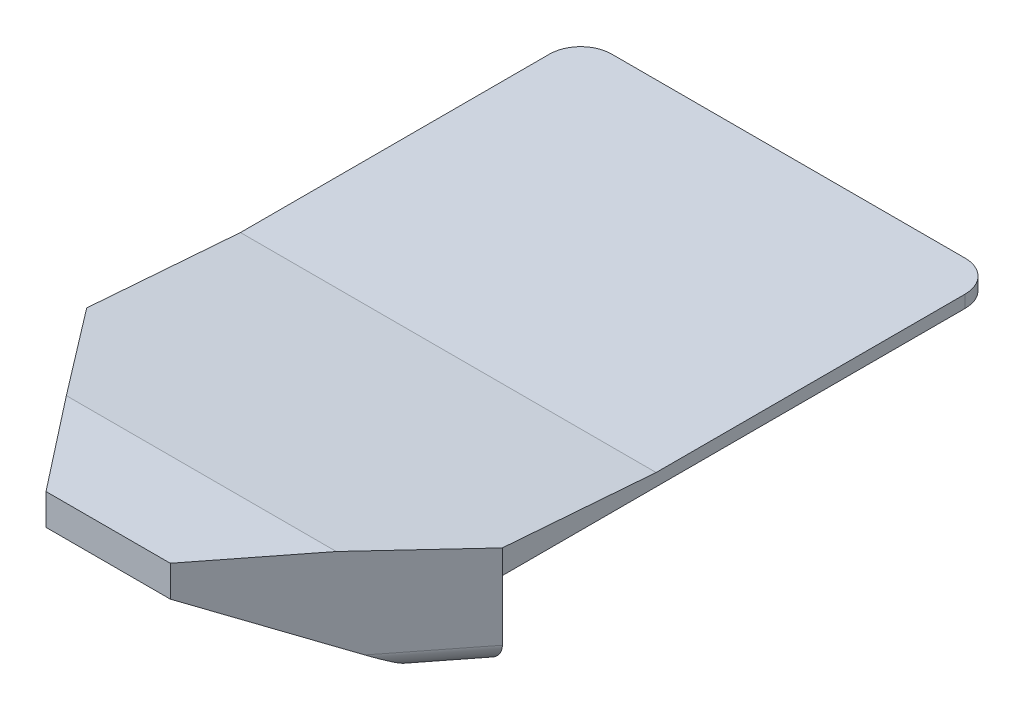
SolidWorks part; units mm, degrees
ref_plane "Front Plane" through (0, 0, 0) normal (0, 0, 1) x (1, 0, 0)
ref_plane "Top Plane" through (0, 0, 0) normal (0, 1, 0) x (1, 0, 0)
ref_plane "Right Plane" through (0, 0, 0) normal (1, 0, 0) x (0, 0, -1)
sketch "Sketch1" plane through (0, 0, 0) normal (0, 1, 0) x (1, 0, 0)
  line L0 (0, 0) -> (-16.35, 0)
  line L1 (-16.35, 0) -> (-16.35, -9.85)
  line L2 (-16.35, -9.85) -> (-2.6, -9.85)
  line L3 (-20.1, -33) -> (-20.1, -75)
  line L4 (-20.1, -75) -> (0, -75)
  line L5 (0, -75) -> (0, 0)
  line L6 (-2.6, -9.85) -> (-2.6, -33)
  line L7 (-2.6, -33) -> (-20.1, -33)
  dimension "D1" = 16.35
  dimension "D2" = 9.85
  dimension "D3" = 13.75
  dimension "D4" = 3.75
  dimension "D5" = 23.15
  dimension "D6" = 42
extrude "Boss-Extrude1" add sketch "Sketch1" along normal blind 7.7
sketch "Sketch2" plane through (0, 0, 75) normal (0, 0, 1) x (1, 0, 0)
  line L0 (-20.1, 7.7) -> (-20.1, 0) construction
  line L1 (-20.1, 5.1) -> (-13.1, 5.1)
  line L2 (-20.1, 5.1) -> (-20.1, 2)
  line L3 (-20.1, 2) -> (-13.1, 2)
  line L4 (-13.1, 5.1) -> (-13.1, 2)
  line L5 (-20.1, 0) -> (0, 0) construction
  dimension "D1" = 7
  dimension "D2" = 3.1
  dimension "D3" = 2
extrude "Cut-Extrude1" cut sketch "Sketch2" against normal through all
fillet "Fillet1" radius 10 1 edges at (-2.6, 3.85, 33)
sketch "Sketch3" plane through (0, 7.7, 0) normal (0, 1, 0) x (1, 0, 0)
  line L0 (0, 0) -> (0, -75)
  line L1 (0, -75) -> (-33.45, -75)
  line L2 (-33.45, -75) -> (-33.45, 0)
  line L3 (-33.45, 0) -> (0, 0)
  line L4 (0, -75) -> (0, -105)
  line L5 (0, -105) -> (-10, -105)
  line L6 (0, 0) -> (0, 4.5)
  line L7 (-33.45, -75) -> (-10, -105)
  line L8 (0, 4.5) -> (-33.45, 4.5)
  line L9 (-33.45, 4.5) -> (-33.45, 0)
  dimension "D1" = 33.45
  dimension "D2" = 30
  dimension "D3" = 10
  dimension "D4" = 4.5
extrude "Boss-Extrude2" add sketch "Sketch3" along normal blind 2
sketch "Sketch4" plane through (0, 0, 0) normal (1, 0, 0) x (0, 0, -1)
  line L0 (-105, 9.7) -> (-105, 12.7)
  line L1 (-105, 12.7) -> (-90, 12.7)
  line L2 (-90, 12.7) -> (-50.25, 9.7)
  line L3 (-105, 9.7) -> (4.5, 9.7) construction
  line L4 (-105, 9.7) -> (-50.25, 9.7)
  point P8 (-50.25, 9.7)
  dimension "D1" = 15
  dimension "D2" = 3
extrude "Boss-Extrude3" add sketch "Sketch4" against normal up to surface (33.45 mm away) up to face at (-33.45, 8.7, 35.25)
sketch "Sketch5" plane through (-33.45, 0, 0) normal (-1, 0, 0) x (0, 0, 1)
  line L0 (75, 7.7) -> (75, -5)
  line L1 (75, -5) -> (82, -5)
  line L2 (82, -5) -> (105, 7.7)
  line L3 (105, 7.7) -> (75, 7.7)
  line L4 (33, 0) -> (75, 0) construction
  dimension "D1" = 5
  dimension "D2" = 7
extrude "Boss-Extrude4" add sketch "Sketch5" against normal up to surface (33.45 mm away) up to face at (0, 7.56, 49.125)
sketch "Sketch6" plane through (0, 7.7, 0) normal (0, 1, 0) x (1, 0, 0)
  line L0 (-33.45, -75) -> (-10, -105)
  line L1 (-10, -105) -> (-33.45, -105)
  line L2 (-33.45, -105) -> (-33.45, -75)
extrude "Cut-Extrude2" cut sketch "Sketch6" against normal through all both and the other way through all
sketch "Sketch7" plane through (0, 0, 0) normal (1, 0, 0) x (0, 0, -1)
  line L0 (-75, 0) -> (-85, 0)
  line L1 (-85, 0) -> (-80, -5)
  line L2 (-82, -5) -> (-75, -5) construction
  line L3 (-80, -5) -> (-75, -5)
  line L4 (-75, -5) -> (-75, 0)
  dimension "D1" = 5
  dimension "D2" = 10
extrude "Cut-Extrude3" cut sketch "Sketch7" against normal blind 10
fillet "Fillet3" radius 1 2 edges at (-5, -5, 80) (-10, -5, 77.5)
fillet "Fillet4" radius 5 1 edges at (-33.45, 8.7, -4.5)
mirror "Mirror1" about plane through (0, 7.7, 75) normal (-1, 0, 0) of bodies 110
fillet "Fillet5" radius 3 2 edges at (-30.7142, -5, 78.5) (30.7142, -5, 78.5)
